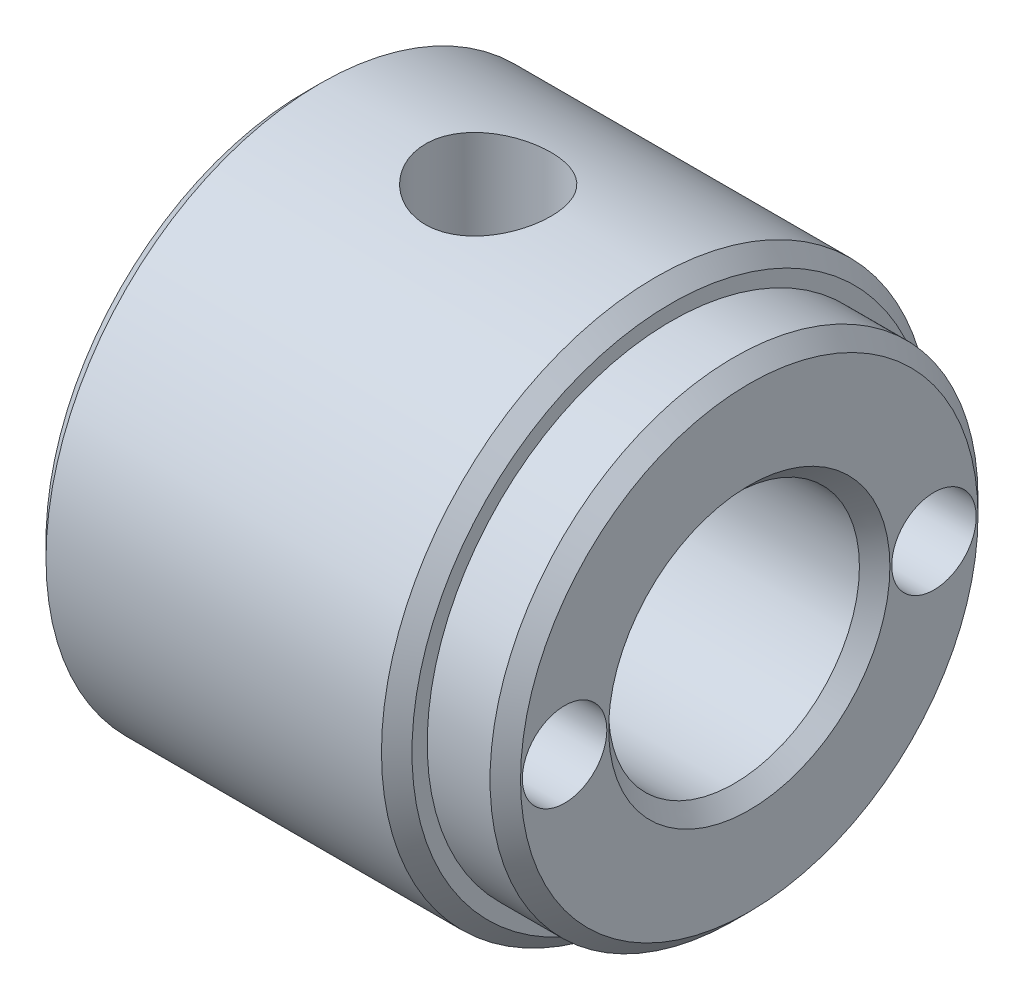
SolidWorks part; units mm, degrees
ref_plane "Front Plane" through (0, 0, 0) normal (0, 0, 1) x (1, 0, 0)
ref_plane "Top Plane" through (0, 0, 0) normal (0, 1, 0) x (1, 0, 0)
ref_plane "Right Plane" through (0, 0, 0) normal (1, 0, 0) x (0, 0, -1)
sketch "Sketch1" plane through (0, 0, 0) normal (1, 0, 0) x (0, 0, -1)
  line L0 (0, 0) -> (0, 0.7417) construction
  line L1 (-3.2639, 0) -> (-6.35, 0) construction
  circle A0 centre (0, 0) radius 6.35
  circle A1 centre (0, 0) radius 6.35
  circle A2 centre (0, 0) radius 3.2639
  circle A3 centre (-4.807, 0) radius 1.1
  circle A5 centre (0, 0) radius 7.1438
  circle A6 centre (4.807, 0) radius 1.1
  point P12 (-4.807, 0)
  dimension "D1" = 12.7
  dimension "D2" = 6.5278
  dimension "D3" = 2.2
  dimension "D4" = 14.2875
extrude "Inner Side Extrude" add sketch "Sketch1" along normal blind 2.032 contours A0 A2 A3 A6 region at (0, 0, 6.1704)
extrude "Outer Side Extrude" add sketch "Sketch1<3>" against normal blind 9.525 contours A0 A2 A3 A6 | A5 A0 region at (0, 0, 6.1704) region at (0, 0, 6.9417)
sketch "Sketch1<3>" plane through (0, 0, 0) normal (1, 0, 0) x (0, 0, -1) same geometry as "Sketch1"
sketch "Sketch2" plane through (0, 0, 0) normal (0, 1, 0) x (1, 0, 0)
  line L0 (-9.525, 7.1438) -> (-9.525, -7.1438) construction
  line L1 (-9.525, 0) -> (0, 0) construction
  circle A0 centre (-4.7625, 0) radius 1.632
  point P0 (-9.525, 0)
  dimension "D1" = 3.2639
extrude "Cut-Extrude1" cut sketch "Sketch2" against normal through all and the other way through all
chamfer "Chamfer so Steve Doesn't cut himself" distance 0.3969 angle 45 5 edges at (-9.525, 0, -3.2639) (2.032, 0, -3.2639) (2.032, 0, -6.35) (-9.525, 0, -7.1438) (0, 0, -7.1438)
